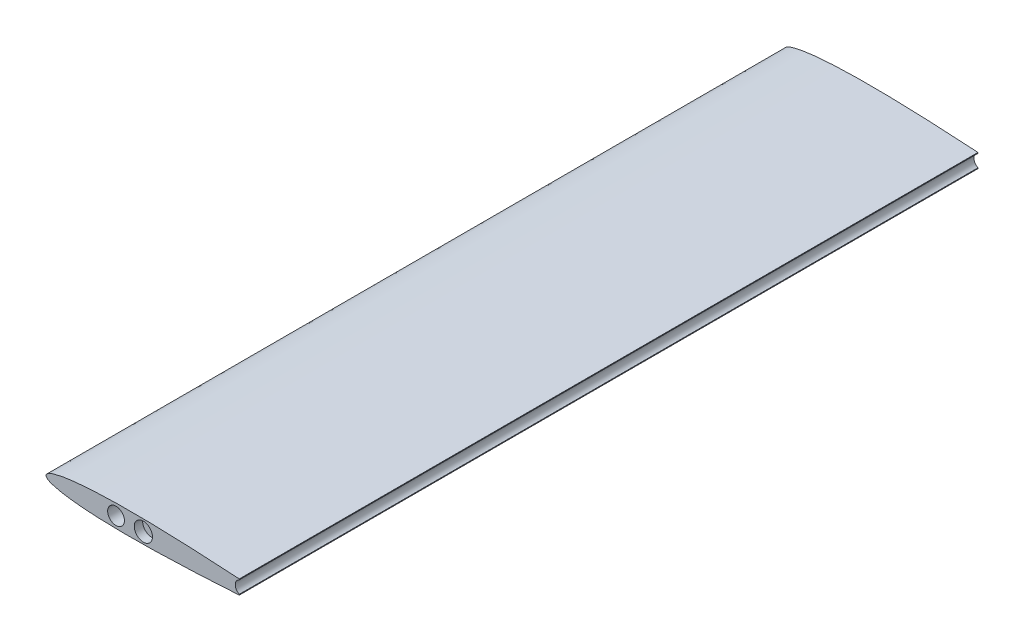
SolidWorks part; units mm, degrees
material "ABS generico"
ref_plane "Piano frontale" through (0, 0, 0) normal (0, 0, 1) x (1, 0, 0)
ref_plane "Piano superiore" through (0, 0, 0) normal (0, 1, 0) x (1, 0, 0)
ref_plane "Piano destro" through (0, 0, 0) normal (1, 0, 0) x (0, 0, -1)
curve "Curva1"
  spline degree 3 poles (100, 0.084, 0) (98.3335, 0.2367, 0) (95.0012, 0.5422, 0) (88.3356, 1.1109, 0) (80.0033, 1.7636, 0) (70.003, 2.4579, 0) (60.0031, 3.0617, 0) (50.003, 3.5521, 0) (40.0026, 3.9029, 0) (31.667, 4.0253, 0) (24.9992, 3.9769, 0) (19.9978, 3.845, 0) (14.9934, 3.5925, 0) (10.8272, 3.2377, 0) (7.4891, 2.814, 0) (4.9936, 2.4037, 0) (2.8496, 1.8679, 0) (1.1654, 1.321, 0) (-0.6646, 0, 0) (1.1654, -1.321, 0) (2.8496, -1.8679, 0) (4.9936, -2.4037, 0) (7.4891, -2.814, 0) (10.8272, -3.2377, 0) (14.9934, -3.5925, 0) (19.9978, -3.845, 0) (24.9992, -3.9769, 0) (31.667, -4.0253, 0) (40.0026, -3.9029, 0) (50.003, -3.5521, 0) (60.0031, -3.0617, 0) (70.003, -2.4579, 0) (80.0033, -1.7636, 0) (88.3356, -1.1109, 0) (95.0012, -0.5422, 0) (98.3335, -0.2367, 0) (100, -0.084, 0) knots 0 0 0 0 0.024876 0.049742 0.099443 0.149112 0.198751 0.248359 0.297937 0.347491 0.372267 0.397051 0.421859 0.446731 0.45922 0.471791 0.48456 0.491195 0.5 0.508805 0.51544 0.528209 0.54078 0.553269 0.578141 0.602949 0.627733 0.652509 0.702063 0.751641 0.801249 0.850888 0.900557 0.950258 0.975124 1 1 1 1
sketch "Schizzo1" plane through (0, 0, 0) normal (0, 0, 1) x (1, 0, 0)
  line L0 (70, 2.443) -> (70, -2.443) construction
  arc A1 (70, 2.443) -> (70, -2.443) centre (70, 0) ccw
  spline S0 degree 3 poles (1029.3323, 4889.466) (420.5539, -80.0474) (258.4436, -13.4031) (88.3356, 1.1109) (80.0033, 1.7636) (70.003, 2.4579) (60.0031, 3.0617) (50.003, 3.5521) (40.0026, 3.9029) (31.667, 4.0253) (24.9992, 3.9769) (19.9978, 3.845) (14.9934, 3.5925) (10.8272, 3.2377) (7.4891, 2.814) (4.9936, 2.4037) (2.8496, 1.8679) (1.1654, 1.321) (-0.6646, 0) (1.1654, -1.321) (2.8496, -1.8679) (4.9936, -2.4037) (7.4891, -2.814) (10.8272, -3.2377) (14.9934, -3.5925) (19.9978, -3.845) (24.9992, -3.9769) (31.667, -4.0253) (40.0026, -3.9029) (50.003, -3.5521) (60.0031, -3.0617) (70.003, -2.4579) (80.0033, -1.7636) (88.3356, -1.1109) (258.4415, 13.4029) (420.5498, 80.0458) (1029.3091, -4889.2764) knots -2.438368 -2.438368 -2.438368 -2.438368 0.024876 0.049742 0.099443 0.149112 0.198751 0.248359 0.297937 0.347491 0.372267 0.397051 0.421859 0.446731 0.45922 0.471791 0.48456 0.491195 0.5 0.508805 0.51544 0.528209 0.54078 0.553269 0.578141 0.602949 0.627733 0.652509 0.702063 0.751641 0.801249 0.850888 0.900557 0.950258 0.975124 3.438336 3.438336 3.438336 3.438336 only from (100, 0.084) to (100, -0.084) construction
  spline S1 degree 3 poles (70, 2.443) (66.6677, 2.6593) (60.0031, 3.0617) (50.003, 3.5521) (40.0026, 3.9029) (31.667, 4.0253) (24.9992, 3.9769) (19.9978, 3.845) (14.9934, 3.5925) (10.8272, 3.2377) (7.4891, 2.814) (4.9936, 2.4037) (2.8496, 1.8679) (1.1654, 1.321) (-0.6646, 0) (1.1654, -1.321) (2.8496, -1.8679) (4.9936, -2.4037) (7.4891, -2.814) (10.8272, -3.2377) (14.9934, -3.5925) (19.9978, -3.845) (24.9992, -3.9769) (31.667, -4.0253) (40.0026, -3.9029) (50.003, -3.5521) (60.0031, -3.0617) (66.6677, -2.6593) (70, -2.443) knots 0.149112 0.149112 0.149112 0.149112 0.198751 0.248359 0.297937 0.347491 0.372267 0.397051 0.421859 0.446731 0.45922 0.471791 0.48456 0.491195 0.5 0.508805 0.51544 0.528209 0.54078 0.553269 0.578141 0.602949 0.627733 0.652509 0.702063 0.751641 0.801249 0.850888 0.850888 0.850888 0.850888
  dimension "D2" = 4.886
extrude "CorpoFoam" add sketch "Schizzo1" along normal blind 263.67
sketch "Schizzo2" plane through (0, 0, 263.67) normal (0, 0, 1) x (1, 0, 0)
  line L0 (72, 0) -> (70, 0) construction
  line L1 (72, 2.5074) -> (69, 2.5074)
  line L2 (72, 2.5074) -> (72, -2.5074)
  line L3 (72, -2.5074) -> (69, -2.5074)
  line L4 (69, 2.5074) -> (69, -2.5074)
  arc A0 (70, 2.443) -> (70, -2.443) centre (70, 0) ccw construction
  spline S0 degree 3 poles (70, 2.443) (66.6677, 2.6593) (60.0031, 3.0617) (50.003, 3.5521) (40.0026, 3.9029) (31.667, 4.0253) (24.9992, 3.9769) (19.9978, 3.845) (14.9934, 3.5925) (10.8272, 3.2377) (7.4891, 2.814) (4.9936, 2.4037) (2.8496, 1.8679) (1.1654, 1.321) (-0.6646, 0) (1.1654, -1.321) (2.8496, -1.8679) (4.9936, -2.4037) (7.4891, -2.814) (10.8272, -3.2377) (14.9934, -3.5925) (19.9978, -3.845) (24.9992, -3.9769) (31.667, -4.0253) (40.0026, -3.9029) (50.003, -3.5521) (60.0031, -3.0617) (66.6677, -2.6593) (70, -2.443) knots 0.149112 0.149112 0.149112 0.149112 0.198751 0.248359 0.297937 0.347491 0.372267 0.397051 0.421859 0.446731 0.45922 0.471791 0.48456 0.491195 0.5 0.508805 0.51544 0.528209 0.54078 0.553269 0.578141 0.602949 0.627733 0.652509 0.702063 0.751641 0.801249 0.850888 0.850888 0.850888 0.850888 construction
  dimension "D1" = 3
  dimension "D2" = 1
extrude "SmussoPosteriore" cut sketch "Schizzo2" against normal through all
sketch "Schizzo3" plane through (0, 0, 263.67) normal (0, 0, 1) x (1, 0, 0)
  circle A0 centre (25, 0) radius 3
  dimension "D1" = 6
  dimension "D2" = 25
extrude "ForoLongherone" cut sketch "Schizzo3" against normal through all
ref_plane "PianoMedio" through (0, 0, 140) normal (0, 0, 1) x (1, 0, 0)
sketch "Schizzo4" plane through (0, 0, 263.67) normal (0, 0, 1) x (1, 0, 0)
  line L0 (25, 0) -> (34.75, 0) construction
  line L7 (28, 3.995) -> (28, -3.995) construction
  line L8 (31.5, 3.9977) -> (31.5, -3.9977) construction
  circle A0 centre (34.75, 0) radius 3.25
  circle A2 centre (25, 0) radius 3 construction
  spline S0 degree 3 poles (69, 2.5074) (66.0008, 2.6994) (59.6695, 3.0781) (50.003, 3.5521) (40.0026, 3.9029) (31.667, 4.0253) (24.9992, 3.9769) (19.9978, 3.845) (14.9934, 3.5925) (10.8272, 3.2377) (7.4891, 2.814) (4.9936, 2.4037) (2.8496, 1.8679) (1.1654, 1.321) (-0.6646, 0) (1.1654, -1.321) (2.8496, -1.8679) (4.9936, -2.4037) (7.4891, -2.814) (10.8272, -3.2377) (14.9934, -3.5925) (19.9978, -3.845) (24.9992, -3.9769) (31.667, -4.0253) (40.0026, -3.9029) (50.003, -3.5521) (59.6695, -3.0781) (66.0008, -2.6994) (69, -2.5074) knots 0.154077 0.154077 0.154077 0.154077 0.198751 0.248359 0.297937 0.347491 0.372267 0.397051 0.421859 0.446731 0.45922 0.471791 0.48456 0.491195 0.5 0.508805 0.51544 0.528209 0.54078 0.553269 0.578141 0.602949 0.627733 0.652509 0.702063 0.751641 0.801249 0.845923 0.845923 0.845923 0.845923 construction
  dimension "D1" = 6.5
  dimension "D2" = 3.5
extrude "TestaViteSinistra" cut sketch "Schizzo4" against normal blind 3
ref_plane "VeroPianoMedio" through (0, 0, 131.835) normal (0, 0, 1) x (1, 0, 0)
mirror "TestaViteDestra" about plane through (0, 0, 131.835) normal (0, 0, 1) of "TestaViteSinistra"
sketch "Schizzo5" plane through (0, 0, 0) normal (0, 1, 0) x (1, 0, 0)
  line L1 (30, -131.835) -> (55, -131.835)
  line L2 (30, -131.835) -> (30, -95.835)
  line L3 (30, -95.835) -> (55, -95.835)
  line L4 (55, -131.835) -> (55, -95.835)
  line L5 (-4.4278, -131.835) -> (4.4278, -131.835) construction
  line L16 (25, -263.67) -> (25, -131.835) construction
  dimension "D1" = 36
  dimension "D2" = 25
  dimension "D3" = 5
extrude "IncassoServomotore" cut sketch "Schizzo5" against normal blind 10 and the other way blind 1
sketch "Schizzo6" plane through (0, 0, 95.835) normal (0, 0, 1) x (1, 0, 0)
  line L0 (30, 1) -> (30, -4.001) construction
  line L1 (34.5, -4.001) -> (30, -4.001)
  line L2 (34.5, -4.001) -> (34.5, -2.301)
  line L3 (34.5, -2.301) -> (30, -2.301)
  line L4 (30, -4.001) -> (30, -2.301)
  point P6 (0, 0)
  point P7 (0, 0)
  dimension "D1" = 4.5
  dimension "D2" = 1.7
extrude "CanaleCaviServomotore" cut sketch "Schizzo6" against normal blind 91
fillet "Raccordo1" radius 10 1 edges at (32.25, -2.301, 4.835)
